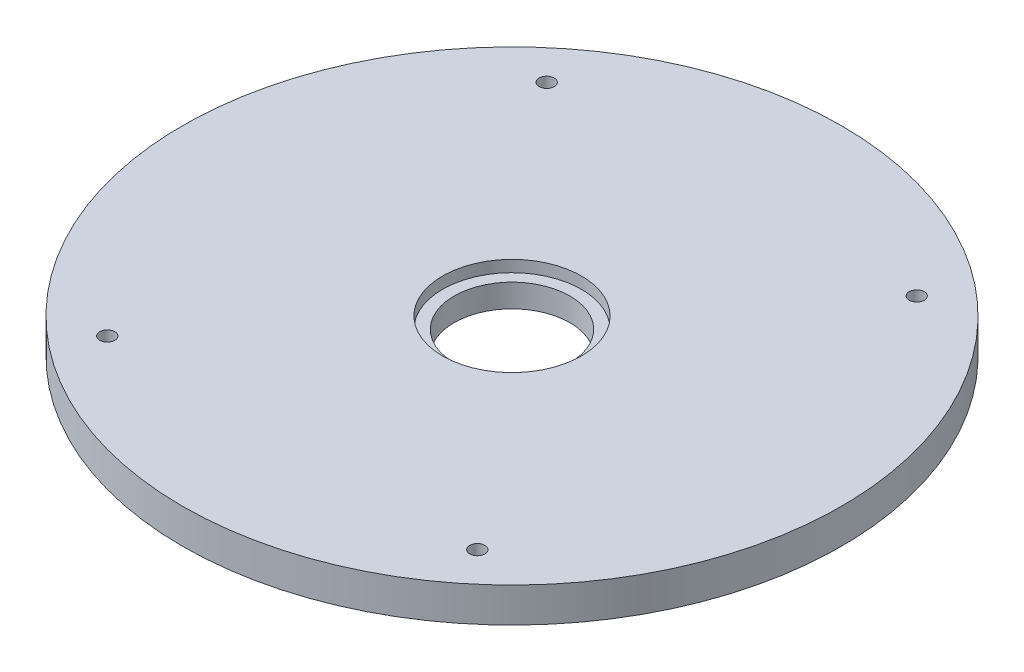
SolidWorks part; units mm, degrees
ref_plane "Front Plane" through (0, 0, 0) normal (0, 0, 1) x (1, 0, 0)
ref_plane "Top Plane" through (0, 0, 0) normal (0, 1, 0) x (1, 0, 0)
ref_plane "Right Plane" through (0, 0, 0) normal (1, 0, 0) x (0, 0, -1)
sketch "MountingHoles" plane through (0, 0, 0) normal (0, 1, 0) x (1, 0, 0)
  circle A0 centre (-80, 95) radius 3.25
  circle A1 centre (-80, -95) radius 3.25
  circle A2 centre (80, -95) radius 3.25
  circle A3 centre (80, 95) radius 3.25
  dimension "D1" = 6.5
  dimension "D2" = 190
  dimension "D3" = 160
  dimension "D4" = 80
  dimension "D5" = 95
sketch "BaseSketch" plane through (0, 0, 0) normal (0, 1, 0) x (1, 0, 0)
  circle A0 centre (0, 0) radius 142.5
  dimension "D1" = 285
extrude "Base" add sketch "BaseSketch" along normal blind 15
extrude "Cut-Extrude1" cut sketch "MountingHoles" along normal up to surface (15 mm away) up to face at (0, 15, 142.5)
sketch "BearingJ1" plane through (0, 0, 0) normal (0, 1, 0) x (1, 0, 0)
  circle A0 centre (0, 0) radius 25
  dimension "D1" = 50
extrude "Cut-Extrude3" cut sketch "BearingJ1" along direction (0, 1, 0) on the side of the normal up to next (15 mm away) contours A0
sketch "Sketch4" plane through (0, 15, 0) normal (0, 1, 0) x (1, 0, 0)
  line L1 (-62.5, -100) -> (62.5, -100) construction
  line L2 (-62.5, -100) -> (-62.5, 100) construction
  line L3 (-62.5, 100) -> (62.5, 100) construction
  line L4 (62.5, -100) -> (62.5, 100) construction
  line L5 (-62.5, -100) -> (62.5, 100) construction
  line L6 (-62.5, 100) -> (62.5, -100) construction
  circle A0 centre (0, 0) radius 75 construction
  dimension "D1" = 150
  dimension "D2" = 125
  dimension "D3" = 200
sketch "Sketch7" plane through (0, 15, 0) normal (0, 1, 0) x (1, 0, 0)
  line L0 (-62.5, -100) -> (-62.5, 100) construction
  line L1 (-62.5, 100) -> (62.5, 100) construction
  line L2 (-62.5, 80) -> (-62.5, 5) construction
  line L3 (0, 138.2666) -> (0, -138.2666) construction
  circle A0 centre (-62.5, 80) radius 3.5
  circle A1 centre (-62.5, 5) radius 3.5
  circle A2 centre (-62.5, -70) radius 3.5
  circle A3 centre (62.5, -70) radius 3.5
  circle A4 centre (62.5, 5) radius 3.5
  circle A5 centre (62.5, 80) radius 3.5
  point P14 (0, 0)
  dimension "D1" = 7
  dimension "D2" = 20
  dimension "D4" = 75
  dimension "D3" = 3
sketch "BearingRadialConstraint" plane through (0, 0, 0) normal (0, 1, 0) x (1, 0, 0)
  circle A0 centre (0, 0) radius 30
  dimension "D1" = 60
extrude "Cut-Extrude4" cut sketch "BearingRadialConstraint" against normal blind 5 from surface starting at face at (0, 15, 25)
